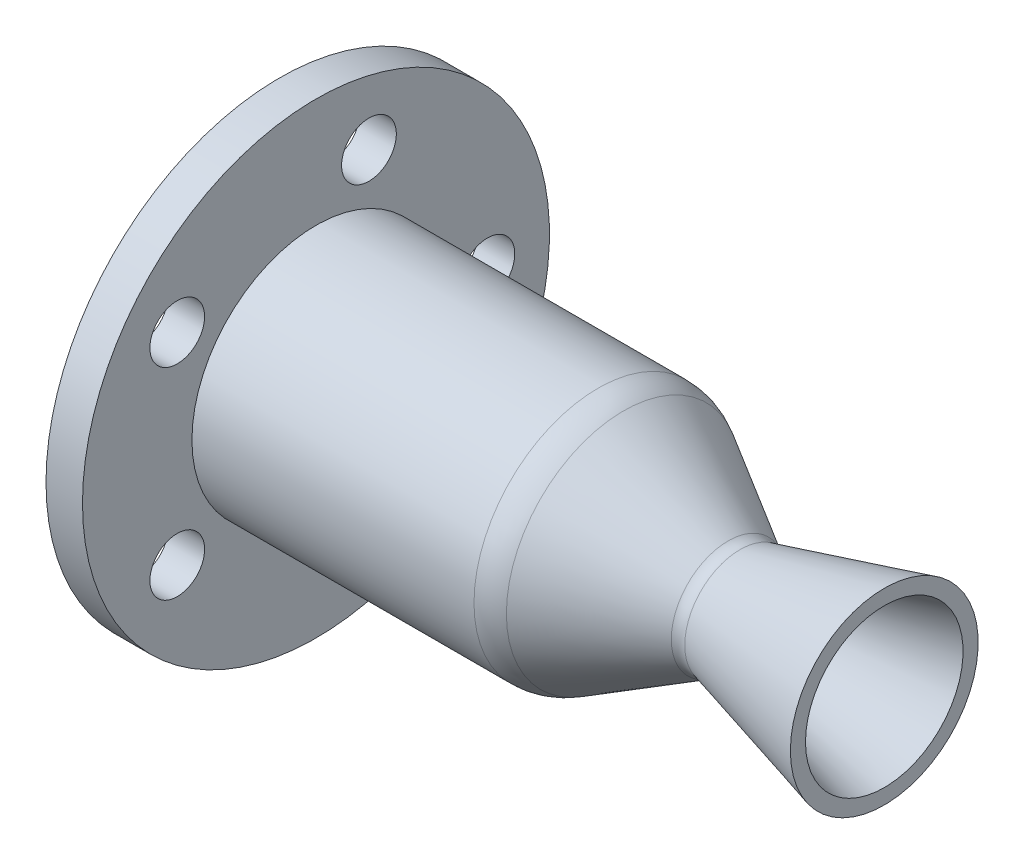
SolidWorks part; units mm, degrees
material "AISI 304"
ref_plane "Front Plane" through (0, 0, 0) normal (0, 0, 1) x (1, 0, 0)
ref_plane "Top Plane" through (0, 0, 0) normal (0, 1, 0) x (1, 0, 0)
ref_plane "Right Plane" through (0, 0, 0) normal (1, 0, 0) x (0, 0, -1)
sketch "Sketch1" plane through (0, 0, 0) normal (0, 0, 1) x (1, 0, 0)
  line L0 (0, 0) -> (366.3783, 0) construction
  line L1 (0, 0) -> (0, 38.1) construction
  line L2 (0, 38.1) -> (110.897, 38.1)
  line L3 (158.9188, 24.511) -> (158.9188, 13.97) construction
  line L4 (117.247, 36.3985) -> (153.6483, 15.3822)
  line L5 (150.9294, 13.97) -> (106.9103, 13.97) construction
  line L6 (161.647, 14.3292) -> (210.5452, 27.4314)
  line L7 (210.5452, 27.4314) -> (210.5452, 0) construction
  line L8 (12.7, 43.18) -> (110.897, 43.18)
  line L9 (119.787, 40.7979) -> (156.1883, 19.7816)
  line L10 (160.3322, 19.2361) -> (210.5452, 32.6906)
  line L11 (0, 43.18) -> (0, 38.1)
  line L12 (210.5452, 27.4314) -> (210.5452, 32.6906)
  line L13 (160.3322, 19.2361) -> (209.2304, 32.3383) construction
  line L14 (0, 43.18) -> (0, 81.28)
  line L15 (0, 81.28) -> (12.7, 81.28)
  line L16 (12.7, 81.28) -> (12.7, 43.18)
  line L17 (0, 43.18) -> (110.897, 43.18) construction
  arc A0 (153.6483, 15.3822) -> (161.647, 14.3292) centre (158.9188, 24.511) ccw
  arc A1 (110.897, 38.1) -> (117.247, 36.3985) centre (110.897, 25.4) cw
  arc A2 (110.897, 43.18) -> (119.787, 40.7979) centre (110.897, 25.4) cw
  arc A3 (156.1883, 19.7816) -> (160.3322, 19.2361) centre (158.9188, 24.511) ccw
  point P16 (114.3, 38.1)
  dimension "D4" = 21.082
  dimension "D9" = 12.7
  dimension "D1" = 38.1
  dimension "D2" = 114.3
  dimension "D5" = 30
  dimension "D6" = 15
  dimension "D7" = 27.4314
  dimension "D11" = 12.7
  dimension "D12" = 38.1
  dimension "D10" = 5.08
revolve "Revolve1" add sketch "Sketch1" angle 360 about L0
sketch "Sketch2" plane through (0, 0, 0) normal (-1, 0, 0) x (0, 0, 1)
  line L0 (-38.1, 0) -> (-81.28, 0) construction
  circle A0 centre (0, 0) radius 38.1 construction
  circle A1 centre (0, 0) radius 38.1 construction
  circle A2 centre (0, 0) radius 81.28 construction
  circle A3 centre (-59.69, 0) radius 9.525
  circle A4 centre (-18.4452, 56.7686) radius 9.525
  circle A5 centre (48.2902, 35.0849) radius 9.525
  circle A6 centre (48.2902, -35.0849) radius 9.525
  circle A7 centre (-18.4452, -56.7686) radius 9.525
  point P22 (0, 0)
  dimension "D1" = 19.05
  dimension "D2" = 5
extrude "Cut-Extrude1" cut sketch "Sketch2" against normal through all
equation "\"l_star\"= .8m'characteristic length"
equation "\"R_t\"= .55in'throat radius"
equation "\"V_c\"= \"l_star\" * \"R_t\"'chamber volume"
equation "\"D_c\"= 3in'chamber diameter"
equation "\"L_c\"= \"V_c\" / ( ( pi * \"D_c\" ) / 4 )'chamber length"
equation "\"eps_x\"= 3.8557'expansion ratio"
equation "\"D_e\"= \"R_t\" * 2 * sqr ( \"eps_x\" )'exit diameter"
equation "\"arc_t\"= 1.5in * \"R_t\"'arc between convergent and divergent"
equation "\"D3@Sketch1\"=\"R_t\""
equation "\"D7@Sketch1\"=\"D_e\"/2"
equation "\"D1@Sketch1\"=\"D_c\"/2"
